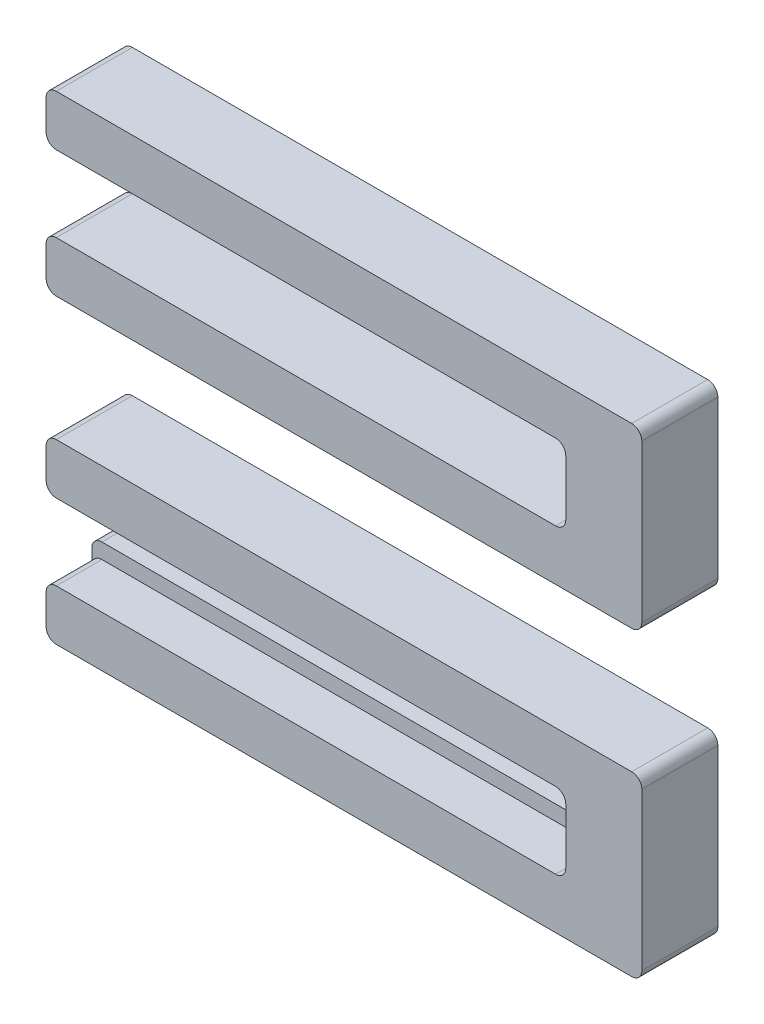
SolidWorks part; units mm, degrees
ref_plane "Front Plane" through (0, 0, 0) normal (0, 0, 1) x (1, 0, 0)
ref_plane "Top Plane" through (0, 0, 0) normal (0, 1, 0) x (1, 0, 0)
ref_plane "Right Plane" through (0, 0, 0) normal (1, 0, 0) x (0, 0, -1)
sketch "Sketch2" plane through (0, 0, 0) normal (0, 0, 1) x (1, 0, 0)
  line L0 (-2.7742, -2.4497) -> (31.3823, -2.4497) construction
  line L1 (0, 0) -> (23.5, 0)
  line L2 (0, 0) -> (0, 7)
  line L3 (0, 7) -> (23.5, 7)
  line L4 (23.5, 0) -> (23.5, 7)
  line L5 (0, 5) -> (20.5, 5)
  line L6 (0, 5) -> (0, 2)
  line L7 (0, 2) -> (20.5, 2)
  line L8 (20.5, 5) -> (20.5, 2)
  line L9 (0, 5) -> (20.5, 5)
  line L10 (0, 5) -> (0, 4.4)
  line L11 (0, 4.4) -> (20.5, 4.4)
  line L12 (20.5, 5) -> (20.5, 4.4)
  line L13 (20.5, -9.8995) -> (20.5, -9.2995)
  line L14 (0, -9.2995) -> (20.5, -9.2995)
  line L15 (0, -9.8995) -> (0, -9.2995)
  line L16 (0, -9.8995) -> (20.5, -9.8995)
  line L17 (20.5, -9.8995) -> (20.5, -6.8995)
  line L18 (0, -6.8995) -> (20.5, -6.8995)
  line L19 (0, -9.8995) -> (0, -6.8995)
  line L20 (0, -9.8995) -> (20.5, -9.8995)
  line L21 (23.5, -4.8995) -> (23.5, -11.8995)
  line L22 (0, -11.8995) -> (23.5, -11.8995)
  line L23 (0, -4.8995) -> (0, -11.8995)
  line L24 (0, -4.8995) -> (23.5, -4.8995)
  dimension "D1" = 7
  dimension "D2" = 3
  dimension "D3" = 2
  dimension "D4" = 3
  dimension "D5" = 20.5
  dimension "D6" = 2.4
extrude "Boss-Extrude1" add sketch "Sketch2" along normal blind 3 contours L5 L8 L7 L2 L1 L4 L3 | L24 L23 L18 L17 L13 L16 L22 L21 region at (0.2452, 1, 0) region at (20.7452, -9.5995, 0)
extrude "Boss-Extrude3" add sketch "Sketch2<4>" along normal blind 1.2 contours L15 L16 L13 L14 | L6 L11 L8 L5 region at (10.25, 4.7, 0) region at (10.25, -9.5995, 0)
sketch "Sketch2<4>" plane through (0, 0, 0) normal (0, 0, 1) x (1, 0, 0) same geometry as "Sketch2"
fillet "Fillet2" radius 0.4 10 edges at (0, 5, 2.1) (20.5, 2, 1.5) (20.5, 4.4, 0.6) (20.5, 5, 2.1) (23.5, 7, 1.5) (23.5, 0, 1.5) (0, 0, 1.5) (0, 2, 1.5) (0, 4.4, 0.6) (0, 7, 1.5)
fillet "Fillet3" radius 0.4 10 edges at (23.5, -11.8995, 1.5) (23.5, -4.8995, 1.5) (20.5, -6.8995, 1.5) (20.5, -9.8995, 2.1) (20.5, -9.2995, 0.6) (0, -11.8995, 1.5) (0, -9.8995, 2.1) (0, -9.2995, 0.6) (0, -4.8995, 1.5) (0, -6.8995, 1.5)
